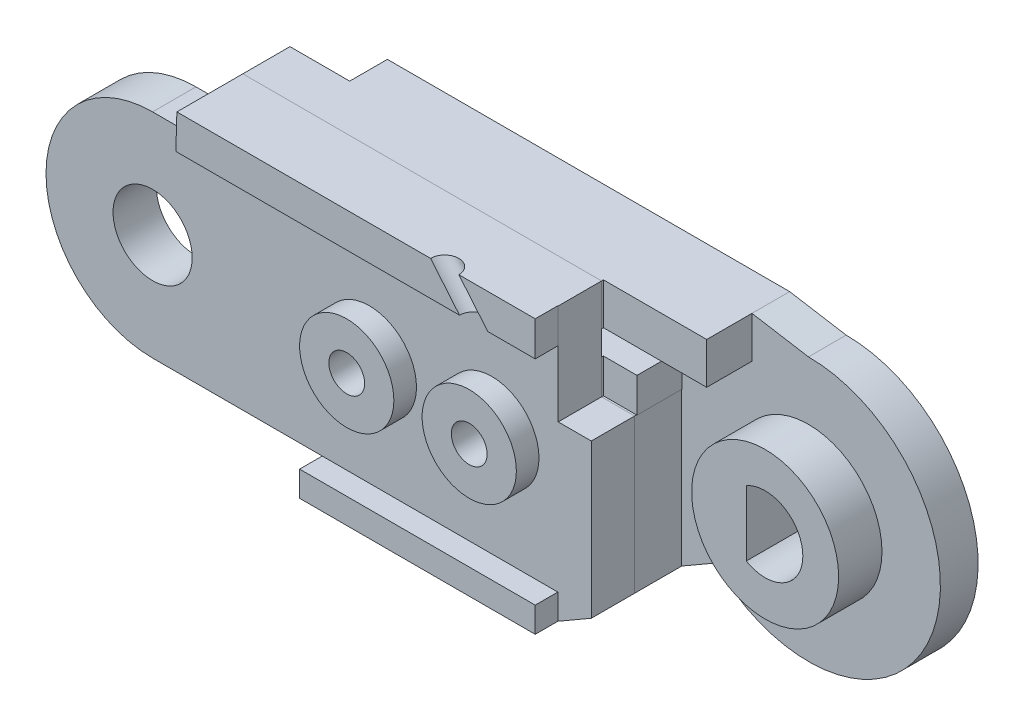
SolidWorks part; units mm, degrees
ref_plane "Front Plane" through (0, 0, 0) normal (0, 0, 1) x (1, 0, 0)
ref_plane "Top Plane" through (0, 0, 0) normal (0, 1, 0) x (1, 0, 0)
ref_plane "Right Plane" through (0, 0, 0) normal (1, 0, 0) x (0, 0, -1)
sketch "Sketch3" plane through (0, 0, 0) normal (0, 0, 1) x (1, 0, 0)
  line L7 (8, 0) -> (9, -2.5)
  line L11 (30, 7) -> (27, 7.5)
  line L13 (0, 7) -> (0, 7.5) construction
  line L14 (0, 7.5) -> (-22.3287, 7.5) construction
  line L15 (0, 5.3) -> (-14, 5.3) construction
  line L16 (0, 4) -> (-14, 4) construction
  line L17 (-14, 4) -> (-14, 5.3) construction
  line L18 (5.6569, 5.6569) -> (5.6569, 7.5)
  line L19 (5.6569, 7.5) -> (27, 7.5)
  line L20 (21.5, -7) -> (9, -7)
  line L21 (9, -7) -> (9, -2.5)
  line L23 (25.0503, -4.9497) -> (21.5, -7)
  arc A4 (8, 0) -> (5.6569, 5.6569) centre (0, 0) ccw
  arc A5 (25.0503, -4.9497) -> (30, 7) centre (30, 0) ccw
  circle A6 centre (0, 0) radius 7 construction
  circle A7 centre (0, 0) radius 3.9 construction
  circle A8 centre (0, 0) radius 5.3 construction
  circle A9 centre (0, 0) radius 4 construction
  dimension "D10" = 0.5
  dimension "D17" = 14
  dimension "D5" = 135
  dimension "D6" = 12.5
  dimension "D7" = 4.5
  dimension "D8" = 1
  dimension "D9" = 45
  dimension "D11" = 1.8431
  dimension "D12" = 30
  dimension "D14" = 3
extrude "Boss-Extrude1" add sketch "Sketch3" along normal blind 2 contours A5 L11 L19 L18 A4 L7 L21 L20 L23
sketch "Sketch20" plane through (0, 0, 0) normal (0, 0, 1) x (1, 0, 0)
  line L0 (0, 7) -> (0, 7.5) construction
  line L1 (0, 7.5) -> (-19.4737, 7.5) construction
  line L2 (0, 5.3) -> (-14, 5.3) construction
  line L3 (0, 4) -> (-14, 4) construction
  line L4 (-14, 4) -> (-14, 5.3) construction
  line L5 (0, 5.3) -> (17.4849, 5.3) construction
  line L6 (17.4849, 5.3) -> (17.4849, 4) construction
  line L7 (17.4849, 4) -> (0, 4) construction
  line L8 (-2.5, 7.5) -> (-2.5, 2.868) construction
  circle A0 centre (0, 0) radius 7 construction
  circle A1 centre (0, 0) radius 3.9 construction
  circle A3 centre (0, 0) radius 5.3 construction
  circle A4 centre (0, 0) radius 4 construction
  circle A5 centre (0, 0) radius 2 construction
  dimension "D1" = 0
  dimension "D2" = 2.5
ref_plane "Plane1" through (0, 0, 2) normal (0, 0, 1) x (1, 0, 0)
sketch "Sketch4" plane through (0, 0, 2) normal (0, 0, 1) x (1, 0, 0)
  line L4 (5.6569, 5.6569) -> (5.6569, 7.5)
  line L5 (5.6569, 5.6569) -> (5.6569, 7.5) construction
  line L6 (5.6569, 7.5) -> (21.5, 7.5)
  line L10 (8, 0) -> (9, -2.5)
  line L11 (9, -2.5) -> (9, -7)
  line L12 (9, -7) -> (21.5, -7)
  line L13 (21.5, -7) -> (21.5, 7.5)
  arc A0 (8, 0) -> (5.6569, 5.6569) centre (0, 0) ccw construction
  arc A3 (8, 0) -> (5.6569, 5.6569) centre (0, 0) ccw
sketch "Sketch22" plane through (0, 0, 2) normal (0, 0, 1) x (1, 0, 0)
  line L0 (5.6569, 5.6569) -> (2.4868, 5.6569)
  line L1 (5.6569, 7.5) -> (21.5, 7.5)
  line L2 (5.6569, 7.5) -> (2.4868, 7.5)
  line L3 (2.4868, 7.5) -> (2.4868, 5.6569)
  line L6 (8, 0) -> (9, -2.5)
  line L7 (9, -2.5) -> (9, -7)
  line L8 (9, -7) -> (21.5, -7)
  line L10 (21.5, 7.5) -> (27, 7.5)
  line L11 (27, 7.5) -> (27, 2.172)
  line L12 (27, 2.172) -> (23.2751, 2.172)
  line L13 (21.5, -7) -> (23.2751, -5.9749)
  line L14 (25.0503, -4.9497) -> (21.5, -7) construction
  line L15 (23.2751, -5.9749) -> (23.2751, 2.172)
  arc A0 (8, 0) -> (5.6569, 5.6569) centre (0, 0) ccw
extrude "Boss-Extrude6" add sketch "Sketch22" along normal blind 2.5
sketch "Sketch25" plane through (0, 0, 2) normal (0, 0, 1) x (1, 0, 0)
  line L0 (0, 5.3) -> (18.0981, 5.3) construction
  line L1 (0, 4) -> (18.0981, 4) construction
  line L2 (18.0981, 4) -> (18.0981, 5.3) construction
sketch "Sketch26" plane through (0, 0, 2) normal (0, 0, 1) x (1, 0, 0)
  line L1 (18.0981, 5.3) -> (2.5301, 5.3)
  line L2 (18.0981, 4) -> (2.5301, 4)
  line L3 (2.5301, 5.3) -> (2.5301, 4)
  line L4 (18.0981, 5.3) -> (27, 5.3)
  line L5 (27, 2.172) -> (27, 7.5) construction
  line L6 (27, 5.3) -> (27, 4)
  line L7 (27, 4) -> (18.0981, 4)
extrude "Cut-Extrude6" cut sketch "Sketch26" along normal blind 2.5
ref_plane "Plane18" through (0, 0, 4.5) normal (0, 0, 1) x (1, 0, 0)
sketch "Sketch31" plane through (0, 0, 4.5) normal (0, 0, 1) x (1, 0, 0)
  line L0 (2.4327, 5.6569) -> (0, 5.6569)
  line L4 (9, -5.6569) -> (0, -5.6569)
  line L5 (2.4327, 5.6569) -> (2.4868, 7.5)
  line L12 (9, -7) -> (9, -5.6569)
  line L13 (9, -2.5) -> (9, -7) construction
  line L16 (27, 7.5) -> (27, 2.172)
  line L17 (27, 2.172) -> (23.2751, 2.172)
  line L18 (23.2751, -5.9749) -> (23.2751, 2.172)
  line L19 (27, 7.5) -> (2.4868, 7.5)
  line L20 (9, -7) -> (21.5, -7)
  line L21 (21.5, -7) -> (23.2751, -5.9749)
  arc A0 (0, 5.6569) -> (0, -5.6569) centre (0, 0) ccw
  dimension "D1" = 5.6569
extrude "Boss-Extrude14" add sketch "Sketch31" along normal blind 2.3 separate body
sketch "Sketch32" plane through (0, 0, 6.8) normal (0, 0, 1) x (1, 0, 0)
  circle A0 centre (0, 0) radius 2.1
extrude "Cut-Extrude7" cut sketch "Sketch32" against normal blind 2.3
sketch "Sketch33" plane through (0, 0, 6.8) normal (0, 0, 1) x (1, 0, 0)
  line L4 (9, -5.6569) -> (9, -7)
  line L11 (9, -7) -> (21.5, -7)
  line L15 (21.5, -7) -> (21.5, -5.6569)
  line L16 (21.5, -5.6569) -> (9, -5.6569)
  line L17 (2.4868, 7.5) -> (21.5, 7.5)
  line L18 (27, 7.5) -> (2.4868, 7.5) construction
  line L19 (2.4868, 7.5) -> (2.4327, 5.6569)
  line L20 (2.4327, 5.6569) -> (21.5, 5.6569)
  line L21 (21.5, 5.6569) -> (21.5, 7.5)
extrude "Boss-Extrude15" add sketch "Sketch33" along normal blind 1.2
sketch "Sketch34" plane through (0, 0, 2) normal (0, 0, 1) x (1, 0, 0)
  line L0 (30, 5.3) -> (18.0981, 5.3) construction
  line L1 (30, 4) -> (18.0981, 4) construction
  circle A0 centre (30, 0) radius 2 construction
  circle A1 centre (30, 0) radius 5.3 construction
  circle A2 centre (30, 0) radius 4 construction
sketch "Sketch35" plane through (0, 0, 6.8) normal (0, 0, 1) x (1, 0, 0)
  line L0 (27, 2.172) -> (27, 7.5)
  line L1 (27, 2.172) -> (21.5204, 2.172)
  line L2 (27, 7.5) -> (21.5204, 7.5)
  line L3 (21.5204, 2.172) -> (21.5204, 7.5)
  line L4 (27, 2.172) -> (27, 7.5) construction
  line L5 (27, 7.5) -> (21.5, 7.5) construction
  dimension "D1" = 0
extrude "Cut-Extrude8" cut sketch "Sketch35" against normal blind 2.4
sketch "Sketch36" plane through (0, 0, 4.4) normal (0, 0, 1) x (1, 0, 0)
  line L0 (27, 2.172) -> (27, 4)
  line L1 (27, 2.172) -> (23.3, 2.172)
  line L2 (27, 4) -> (23.3, 4)
  line L3 (23.3, 2.172) -> (23.3, 4)
  line L4 (21.5, -7) -> (21.5, 7.5) construction
  dimension "D1" = 1.8
extrude "Cut-Extrude9" cut sketch "Sketch36" against normal blind 2.4
sketch "Sketch37" plane through (0, 0, 2) normal (0, 0, 1) x (1, 0, 0)
  circle A0 centre (30, 0) radius 3.9
extrude "Boss-Extrude16" add sketch "Sketch37" along normal blind 2.3
sketch "Sketch39" plane through (0, 0, 4.3) normal (0, 0, 1) x (1, 0, 0)
  line L0 (29, 1.7321) -> (29, -1.7321)
  arc A0 (29, -1.7321) -> (29, 1.7321) centre (30, 0) ccw
  dimension "D2" = 4
  dimension "D1" = 1
extrude "Cut-Extrude10" cut sketch "Sketch39" against normal through all
sketch "Sketch43" plane through (0, 0, 6.8) normal (0, 0, 1) x (1, 0, 0)
  line L2 (0, -5.6569) -> (9, -5.6569) construction
  circle A0 centre (11.5, 0) radius 2.5
  circle A1 centre (18, 0) radius 2.5
  dimension "D1" = 2.5
  dimension "D3" = 5
  dimension "D4" = 6.5
  dimension "D2" = 5.6569
extrude "Boss-Extrude17" add sketch "Sketch43" along normal blind 1.2
sketch "Sketch44" plane through (0, 0, 8) normal (0, 0, 1) x (1, 0, 0)
  circle A0 centre (11.5, 0) radius 0.95
  circle A1 centre (18, 0) radius 0.95
  dimension "D1" = 1.9
  dimension "D2" = 1.9
extrude "Cut-Extrude11" cut sketch "Sketch44" against normal through all
sketch "Sketch45" plane through (0, 0, 0) normal (0, 0, -1) x (-1, 0, 0)
  circle A0 centre (-11.5, 0) radius 2
  circle A1 centre (-18, 0) radius 2
extrude "Cut-Extrude12" cut sketch "Sketch45" against normal blind 2.5
ref_plane "Plane17" through (0, 0, 8) normal (0, 0, 1) x (1, 0, 0)
sketch "Sketch48" plane through (0, 0, 2) normal (0, 0, 1) x (1, 0, 0)
  circle A0 centre (30, 0) radius 5 construction
sketch "Sketch51" plane through (0, 0, 8) normal (0, 0, 1) x (1, 0, 0)
  line L0 (18.2355, 5.6569) -> (27.0112, -4.8677) construction
  line L1 (2.4327, 5.6569) -> (21.5, 5.6569) construction
sketch "Sketch52" plane through (0, 5.6569, 0) normal (0, -1, 0) x (1, 0, 0)
  circle A0 centre (18.2355, 8) radius 0.75
extrude "Cut-Extrude13" cut sketch "Sketch52" along direction (0.6404, -0.768, 0) on the side against the normal blind 10
